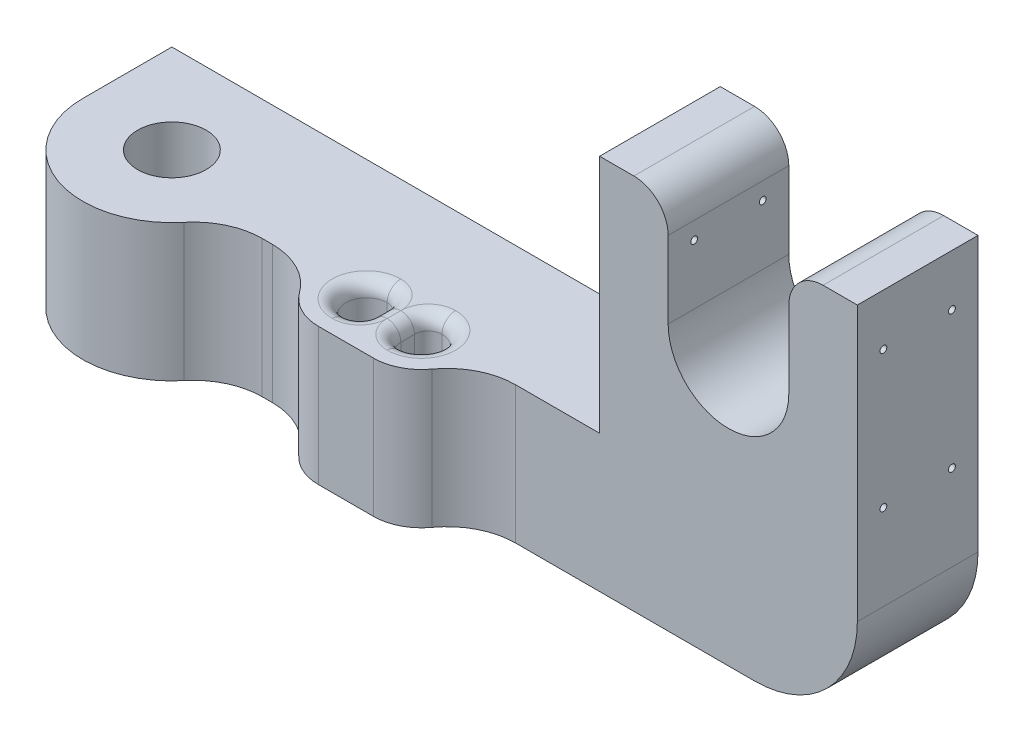
SolidWorks part; units mm, degrees
ref_plane "Front Plane" through (0, 0, 0) normal (0, 0, 1) x (1, 0, 0)
ref_plane "Top Plane" through (0, 0, 0) normal (0, 1, 0) x (1, 0, 0)
ref_plane "Right Plane" through (0, 0, 0) normal (1, 0, 0) x (0, 0, -1)
sketch "Sketch1" plane through (0, 0, 0) normal (0, 0, 1) x (1, 0, 0)
  line L0 (-23.876, -12.7) -> (-23.876, 57.15)
  line L1 (-23.876, 57.15) -> (-17.526, 57.15)
  line L2 (23.876, 57.15) -> (23.876, 12.7)
  line L3 (23.876, 12.7) -> (125.476, 12.7)
  line L4 (125.476, 12.7) -> (125.476, -12.7)
  line L5 (125.476, -12.7) -> (-23.876, -12.7)
  line L6 (-11.176, 50.8) -> (-11.176, 36.576)
  line L7 (11.176, 50.8) -> (11.176, 36.576)
  line L8 (17.526, 57.15) -> (23.876, 57.15)
  line L9 (-17.526, 57.15) -> (17.526, 57.15) construction
  arc A0 (-17.526, 57.15) -> (-11.176, 50.8) centre (-17.526, 50.8) cw
  arc A1 (17.526, 57.15) -> (11.176, 50.8) centre (17.526, 50.8) ccw
  arc A2 (-11.176, 36.576) -> (11.176, 36.576) centre (0, 36.576) ccw
  point P17 (125.476, 0)
  point P20 (0, 57.15)
  dimension "D2" = 6.35
  dimension "D1" = 47.752
  dimension "D3" = 12.7
  dimension "D4" = 12.7
  dimension "D5" = 44.45
  dimension "D6" = 25.4
  dimension "D7" = 12.7
  dimension "D8" = 101.6
extrude "Boss-Extrude1" add sketch "Sketch1" along normal mid plane 22.352
sketch "Sketch2" plane through (0, -12.7, 0) normal (0, -1, 0) x (-1, 0, 0)
  line L0 (-125.476, -5.334) -> (-125.476, -11.176)
  line L1 (-125.476, -11.176) -> (-124.4079, -11.176)
  line L2 (-70.104, 3.81) -> (-67.564, 3.81)
  line L3 (-67.564, 3.81) -> (-67.564, -3.81)
  line L4 (23.876, 11.176) -> (-125.476, 11.176)
  line L5 (-125.476, 11.176) -> (-125.476, -11.176)
  line L6 (-125.476, -11.176) -> (23.876, -11.176)
  line L7 (23.876, -11.176) -> (23.876, 11.176)
  line L8 (23.876, 11.176) -> (-125.476, 11.176) construction
  line L9 (-125.476, 11.176) -> (-125.476, -11.176) construction
  line L10 (-125.476, -11.176) -> (23.876, -11.176) construction
  line L11 (23.876, -11.176) -> (23.876, 11.176) construction
  line L12 (-67.564, -3.81) -> (-70.104, -3.81)
  line L13 (-65.024, 11.176) -> (-65.024, -11.176) construction
  line L14 (-59.944, 3.81) -> (-62.484, 3.81)
  line L15 (-62.484, 3.81) -> (-62.484, -3.81)
  line L16 (-62.484, -3.81) -> (-59.944, -3.81)
  line L17 (23.876, 11.176) -> (-125.476, 11.176) construction
  circle A0 centre (-108.966, -5.334) radius 6.35
  circle A1 centre (-108.966, -5.334) radius 16.51
  arc A2 (-125.476, -5.334) -> (-124.4079, -11.176) centre (-108.966, -5.334) ccw
  arc A4 (-70.104, 3.81) -> (-70.104, -3.81) centre (-70.104, 0) ccw
  arc A5 (-59.944, 3.81) -> (-59.944, -3.81) centre (-59.944, 0) cw
  point P28 (-67.564, 0)
  point P29 (-65.024, 0)
  dimension "D1" = 12.7
  dimension "D3" = 10.16
  dimension "D4" = 7.62
  dimension "D5" = 2.54
  dimension "D6" = 88.9
  dimension "D7" = 2.54
  dimension "D2" = 0
extrude "Cut-Extrude3" cut sketch "Sketch2" against normal through all contours A0 | A2 L1 L0
extrude "Boss-Extrude2" add sketch "Sketch2<4>" against normal up to surface (25.4 mm away) contours A1 region at (108.966, -12.7, 15.6192) up to face at (91.6155, 12.7, 2.2203)
sketch "Sketch2<4>" plane through (0, -12.7, 0) normal (0, -1, 0) x (-1, 0, 0) same geometry as "Sketch2"
sketch "Sketch3" plane through (23.876, 0, 0) normal (1, 0, 0) x (0, 0, -1)
  line L1 (-12.7, 12.7) -> (12.7, 12.7) construction
  line L2 (0, 12.7) -> (0, 57.15) construction
  line L3 (-11.176, 34.925) -> (11.176, 34.925) construction
  line L6 (11.176, 12.7) -> (11.176, 57.15)
  line L7 (11.176, 57.15) -> (-11.176, 57.15)
  line L8 (-11.176, 57.15) -> (-11.176, 12.7)
  line L9 (-11.176, 12.7) -> (11.176, 12.7)
  line L10 (11.176, 12.7) -> (11.176, 57.15) construction
  line L11 (11.176, 57.15) -> (-11.176, 57.15) construction
  line L12 (-11.176, 57.15) -> (-11.176, 12.7) construction
  line L13 (-11.176, 12.7) -> (11.176, 12.7) construction
  circle A0 centre (6.35, 22.225) radius 0.635
  circle A1 centre (-6.35, 22.225) radius 0.635
  circle A2 centre (6.35, 47.625) radius 0.635
  circle A3 centre (-6.35, 47.625) radius 0.635
  dimension "D1" = 9.525
  dimension "D4" = 1.27
  dimension "D3" = 6.35
  dimension "D2" = 0
extrude "Cut-Extrude4" cut sketch "Sketch3" against normal through all
sketch "Sketch4" plane through (0, -12.7, 0) normal (0, -1, 0) x (-1, 0, 0)
  line L0 (-59.436, -14.986) -> (-59.436, -7.366)
  line L1 (-59.436, -7.366) -> (-56.896, -7.366)
  line L2 (-56.896, -14.986) -> (-59.436, -14.986)
  line L3 (-61.976, -21.3901) -> (-61.976, -0.9619) construction
  line L8 (23.876, -11.176) -> (-93.5241, -11.176) construction
  line L9 (-56.896, -20.066) -> (-67.056, -20.066)
  line L11 (-59.436, -11.176) -> (-61.976, -11.176)
  line L12 (-64.516, -7.366) -> (-67.056, -7.366)
  line L15 (-39.4364, -11.176) -> (-53.086, -11.176)
  line L16 (-64.516, -14.986) -> (-64.516, -7.366)
  line L17 (-67.056, -14.986) -> (-64.516, -14.986)
  line L18 (-64.516, -11.176) -> (-61.976, -11.176)
  line L19 (-84.5156, -11.176) -> (-70.866, -11.176)
  line L21 (-23.876, -11.176) -> (-23.876, 11.176) construction
  arc A0 (-56.896, -7.366) -> (-56.896, -14.986) centre (-56.896, -11.176) cw
  arc A2 (-67.056, -7.366) -> (-67.056, -14.986) centre (-67.056, -11.176) ccw
  arc A5 (-49.7067, -16.4054) -> (-39.4364, -11.176) centre (-39.4364, -23.876) cw
  arc A6 (-49.7067, -16.4054) -> (-56.896, -20.066) centre (-56.896, -11.176) cw
  arc A7 (-74.2453, -16.4054) -> (-84.5156, -11.176) centre (-84.5156, -23.876) ccw
  arc A8 (-74.2453, -16.4054) -> (-67.056, -20.066) centre (-67.056, -11.176) ccw
  point P8 (-43.8919, -21.336)
  point P9 (-43.8919, -1.016)
  point P10 (-35.0019, -1.016)
  point P22 (-61.976, -20.066)
  point P34 (-61.976, -20.066)
  dimension "D5" = 12.7
  dimension "D1" = 2.54
  dimension "D2" = 7.62
  dimension "D4" = 2.54
  dimension "D3" = 5.08
  dimension "D6" = 38.1
extrude "Cut-Extrude5" cut sketch "Sketch4" against normal through all contours A0 L1 L0 | L12 A2 L16 | A0 L0 L2 | A2 L17 L16 region at (56.6045, -12.7, 11.176) region at (67.3475, -12.7, 11.176)
extrude "Boss-Extrude3" add sketch "Sketch4<3>" against normal up to surface (25.4 mm away) contours L3 L9 A6 A5 A0 L2 L0 | L9 L3 L16 L17 A2 A7 A8 region at (54.5994, -12.7, 15.4382) region at (69.3526, -12.7, 15.4382) up to face at (108.966, 12.7, -1.016)
sketch "Sketch4<3>" plane through (0, -12.7, 0) normal (0, -1, 0) x (-1, 0, 0) same geometry as "Sketch4"
fillet "Fillet5" radius 2.54 12 edges at (53.086, -12.7, 11.176) (53.086, 12.7, 11.176) (70.866, 12.7, 11.176) (70.866, -12.7, 11.176) (59.436, 0, 14.986) (59.436, -12.7, 11.176) (59.436, 12.7, 11.176) (64.516, 0, 14.986) (64.516, 12.7, 11.176) (59.436, 0, 7.366) (64.516, 0, 7.366) (64.516, -12.7, 11.176)
mirror "Mirror1" about plane through (0, 0, 0) normal (1, 0, 0) of bodies 106
delete or keep bodies "Body-Delete/Keep 1" type delete bodies bodies 106
fillet "Fillet6" radius 19.05 1 edges at (23.876, -12.7, 0)
fillet "Fillet7" [suppressed] radius 19.05
fillet "Fillet8" [suppressed] radius 12.7
fillet "Fillet9" radius 12.7 1 edges at (-93.5241, 0, 11.176)
equation "\"D4@Sketch1\"=\"D3@Sketch1\""
